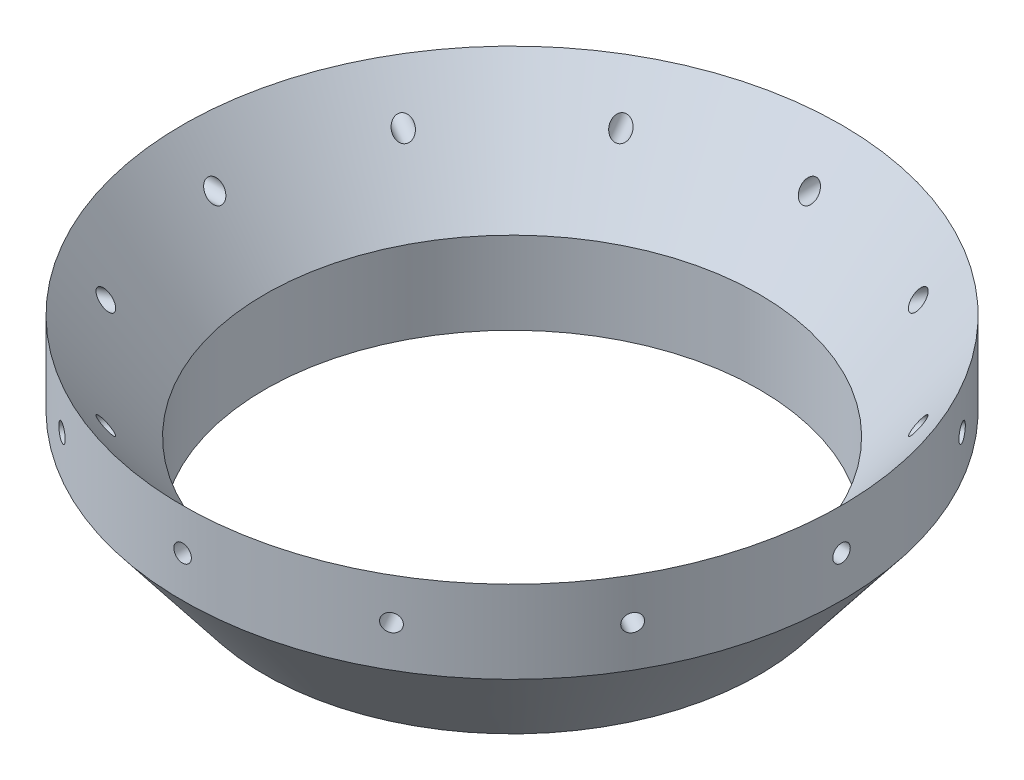
SolidWorks part; units mm, degrees
material "2024-T3"
ref_plane "Front Plane" through (0, 0, 0) normal (0, 0, 1) x (1, 0, 0)
ref_plane "Top Plane" through (0, 0, 0) normal (0, 1, 0) x (1, 0, 0)
ref_plane "Right Plane" through (0, 0, 0) normal (1, 0, 0) x (0, 0, -1)
sketch "Sketch1" plane through (0, 0, 0) normal (0, 0, 1) x (1, 0, 0)
  line L0 (0, 0) -> (0, 220.7687) construction
  line L1 (-57.15, 200.322) -> (-57.15, 219.372)
  line L2 (-57.15, 219.372) -> (-76.2, 243.756)
  line L3 (-76.2, 243.756) -> (-76.2, 224.706)
  line L4 (-76.2, 224.706) -> (-57.15, 200.322)
  dimension "D1" = 57.15
  dimension "D2" = 76.2
  dimension "D3" = 24.384
  dimension "D4" = 19.05
  dimension "D5" = 19.05
revolve "Revolve1" add sketch "Sketch1" angle 360 about L0
sketch "Sketch2" plane through (0, 0, 0) normal (0, 0, 1) x (1, 0, 0)
  line L0 (0, 235.8035) -> (0, 187.481) construction
  line L1 (76.2, 224.706) -> (-76.2, 224.706) construction
  circle A0 centre (0, 234.231) radius 2.0193
  dimension "D1" = 9.525
  dimension "D2" = 4.0386
extrude "Cut-Extrude1" cut sketch "Sketch2" against normal through all
ref_axis "Axis1" through (0, 235.8035, 0) along (0, -1, 0)
pattern_circular "CirPattern1" count 12 over 360 about axis through (0, 235.8035, 0) along (0, -1, 0) of "Cut-Extrude1"
